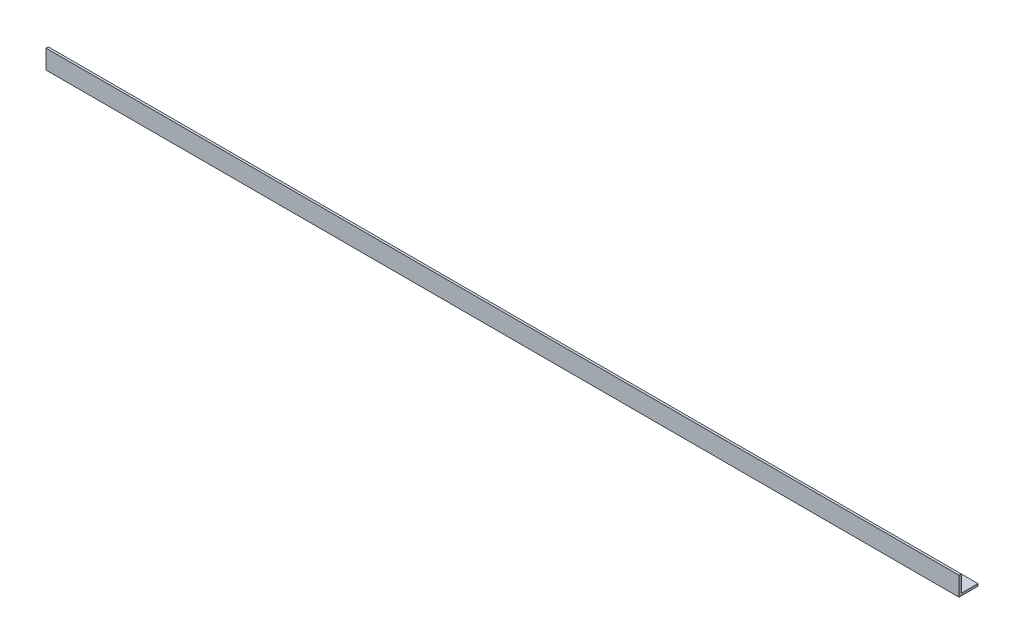
SolidWorks part; units mm, degrees
ref_plane "Спереди" through (0, 0, 0) normal (0, 0, 1) x (1, 0, 0)
ref_plane "Сверху" through (0, 0, 0) normal (0, 1, 0) x (1, 0, 0)
ref_plane "Справа" through (0, 0, 0) normal (1, 0, 0) x (0, 0, -1)
sketch "Эскиз1" plane through (0, 0, 0) normal (1, 0, 0) x (0, 0, -1)
  line L0 (0, 0) -> (0, 25)
  line L1 (0, 0) -> (25, 0)
extrude "Вытянуть-Тонкостенный1" add sketch "Эскиз1" along normal blind 1200 thin thin type one direction reverse wall 3
